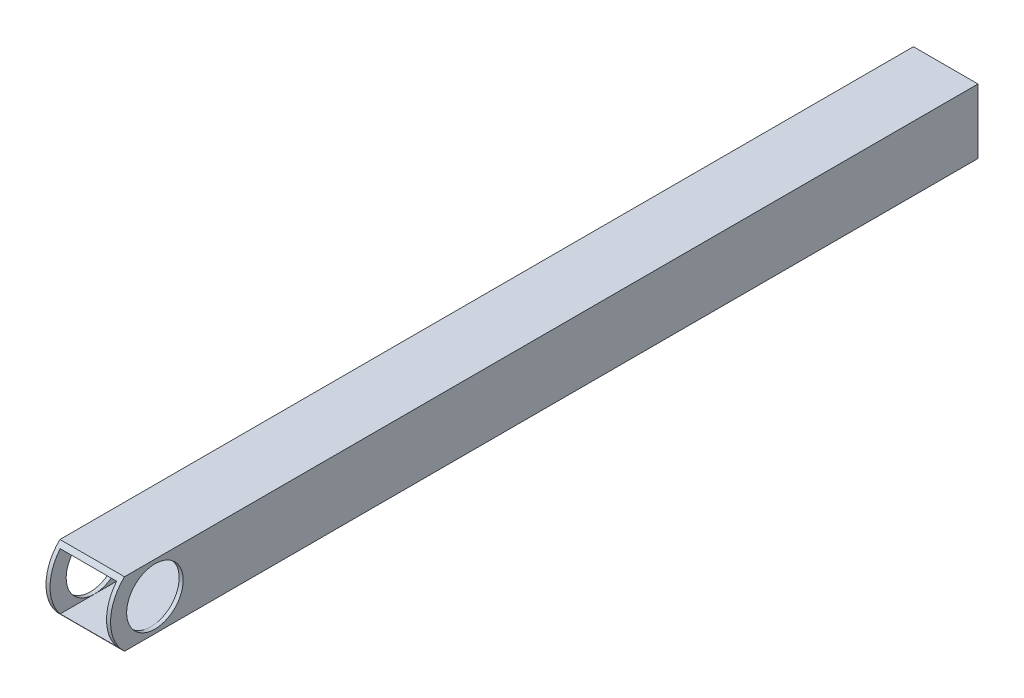
SolidWorks part; units mm, degrees
material "6061 Alloy"
ref_plane "Front Plane" through (0, 0, 0) normal (0, 0, 1) x (1, 0, 0)
ref_plane "Top Plane" through (0, 0, 0) normal (0, 1, 0) x (1, 0, 0)
ref_plane "Right Plane" through (0, 0, 0) normal (1, 0, 0) x (0, 0, -1)
sketch "Sketch1" plane through (0, 0, 0) normal (0, 0, 1) x (1, 0, 0)
  line L1 (12.7, -12.7) -> (-12.7, -12.7)
  line L2 (12.7, -12.7) -> (12.7, 12.7)
  line L3 (12.7, 12.7) -> (-12.7, 12.7)
  line L4 (-12.7, -12.7) -> (-12.7, 12.7)
  line L5 (12.7, -12.7) -> (-12.7, 12.7) construction
  line L6 (12.7, 12.7) -> (-12.7, -12.7) construction
  point P0 (0, 0)
  dimension "D1" = 25.4
extrude "Extrude-Thin1" add sketch "Sketch1" along normal blind 342.9 thin thin type one direction reverse wall 1.5875
sketch "Sketch2" plane through (12.7, 0, 0) normal (1, 0, 0) x (0, 0, -1)
  line L0 (-342.9, -12.7) -> (-342.9, 12.7) construction
  line L1 (-342.9, -12.7) -> (0, -12.7) construction
  circle A0 centre (-323.85, 0) radius 11.1125
  dimension "D1" = 22.225
  dimension "D2" = 19.05
  dimension "D3" = 12.7
extrude "Cut-Extrude1" cut sketch "Sketch2" against normal through all
sketch "Sketch3" plane through (12.7, 0, 0) normal (1, 0, 0) x (0, 0, -1)
  line L0 (-335.8354, 12.7) -> (-342.9, 12.7)
  line L1 (-342.9, 12.7) -> (0, 12.7) construction
  line L2 (-342.9, -12.7) -> (0, -12.7) construction
  line L3 (-342.9, 12.7) -> (-342.9, -12.7)
  line L4 (-342.9, -12.7) -> (-335.8354, -12.7)
  arc A0 (-335.8354, 12.7) -> (-335.8354, -12.7) centre (-323.85, 0) ccw
  circle A1 centre (-323.85, 0) radius 11.1125 construction
  dimension "D1" = 6.35
extrude "Cut-Extrude2" cut sketch "Sketch3" against normal through all
